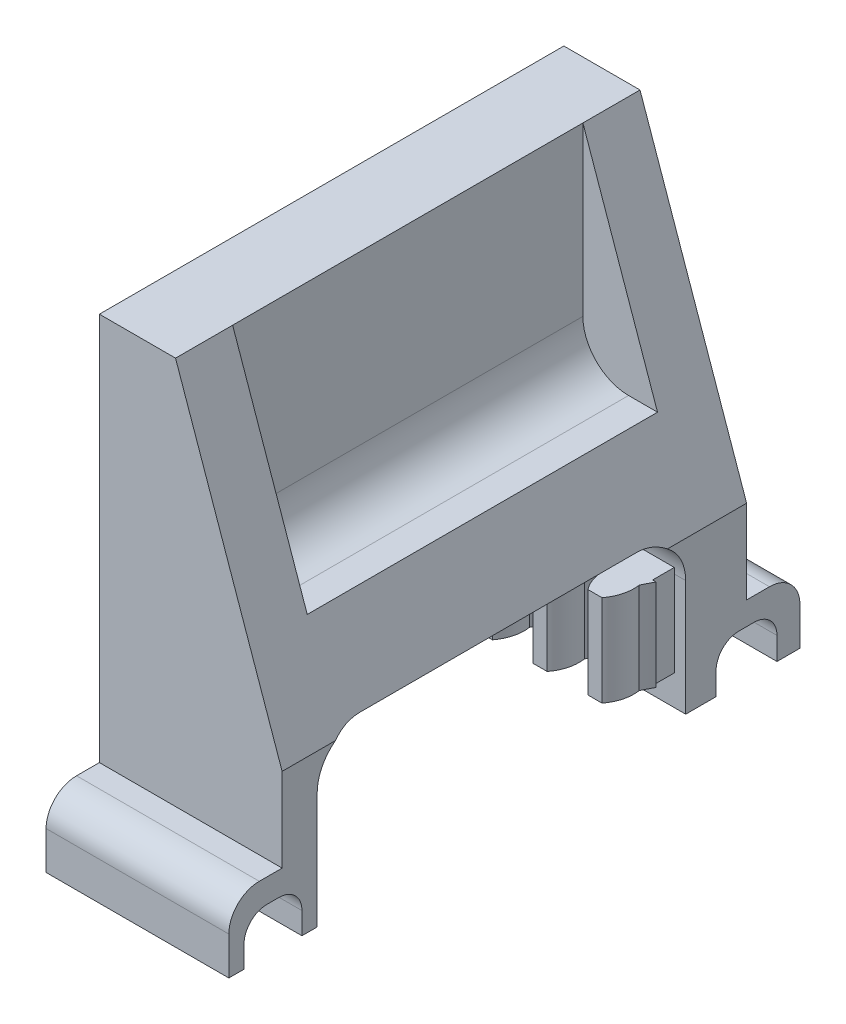
SolidWorks part; units mm, degrees
ref_plane "Front Plane" through (0, 0, 0) normal (0, 0, 1) x (1, 0, 0)
ref_plane "Top Plane" through (0, 0, 0) normal (0, 1, 0) x (1, 0, 0)
ref_plane "Right Plane" through (0, 0, 0) normal (1, 0, 0) x (0, 0, -1)
sketch "Sketch1" plane through (0, 0, 0) normal (0, 0, 1) x (1, 0, 0)
  line L0 (0, 0) -> (0, -30)
  line L1 (0, -30) -> (12, -30)
  line L2 (12, -30) -> (12, -20)
  line L3 (12, -20) -> (5, 0)
  line L4 (5, 0) -> (0, 0)
  dimension "D1" = 30
  dimension "D2" = 12
  dimension "D3" = 10
  dimension "D4" = 5
extrude "Boss-Extrude1" add sketch "Sketch1" against normal blind 30.5
sketch "Sketch4" plane through (0, 0, 0) normal (-1, 0, 0) x (0, 0, 1)
  line L0 (-30.5, 0) -> (-30.5, -30) construction
  line L1 (-26.5, -19.3999) -> (-2.3, -19.3999)
  line L2 (-26.5, -19.3999) -> (-26.5, -32.3999)
  line L3 (-26.5, -32.3999) -> (-2.3, -32.3999)
  line L4 (-2.3, -19.3999) -> (-2.3, -32.3999)
  point P4 (-26.5, -25.8999)
  dimension "D1" = 24.2
  dimension "D2" = 13
  dimension "D3" = 4
extrude "Cut-Extrude2" cut sketch "Sketch4" against normal blind 25 contours L2 L1 L4 L3
ref_plane "Plane1" through (0, 0, -15.25) normal (0, 0, 1) x (1, 0, 0)
sketch "Sketch6" plane through (0, 0, -15.25) normal (0, 0, 1) x (1, 0, 0)
  line L0 (5, 0) -> (5, -14)
  line L1 (5, -14) -> (9.9, -14)
  line L2 (12, -20) -> (5, 0) construction
  line L3 (9.9, -14) -> (5, 0)
  dimension "D1" = 14
extrude "Cut-Extrude4" cut sketch "Sketch6" against normal mid plane 23
ref_plane "Plane2" through (0, -26.4, 0) normal (0, 1, 0) x (1, 0, 0)
ref_plane "Plane3" through (0, -28, 0) normal (0, 1, 0) x (1, 0, 0)
sketch "Sketch7" plane through (0, -28, 0) normal (0, 1, 0) x (1, 0, 0)
  line L0 (11.2768, 26.75) -> (-19.7232, 26.75)
  line L62 (-6.6, 15.25) -> (6.6, 15.25) construction
  line L162 (11.2768, 26.75) -> (11.2768, 25.05)
  line L172 (-19.7232, 25.05) -> (-19.7232, 26.75)
  line L243 (11.2768, 25.05) -> (-19.7232, 25.05)
  dimension "D2" = 31
  dimension "D3" = 1.7
  dimension "D7" = 11.5
extrude "Boss-Extrude3" add sketch "Sketch7" along normal blind 6
sketch "Sketch10" plane through (0, -28, 0) normal (0, 1, 0) x (1, 0, 0)
  line L1 (10.1614, 22.3812) -> (10.1614, 23.4692) construction
  line L2 (10.6216, 22.3812) -> (9.7011, 22.3812)
  line L4 (-19.7232, 25.05) -> (11.2768, 25.05) construction
  line L5 (8.8114, 25.05) -> (11.5114, 25.05)
  arc A0 (10.6216, 22.3812) -> (11.1326, 24.3117) centre (8.6412, 23.9382) ccw
  arc A1 (11.1326, 24.3117) -> (11.5114, 25.05) centre (19.4957, 20.4874) cw
  arc A2 (9.1902, 24.3117) -> (8.8114, 25.05) centre (0.827, 20.4874) ccw
  arc A3 (9.7011, 22.3812) -> (9.1902, 24.3117) centre (11.6815, 23.9382) cw
  point P7 (9.3814, 24.3567)
  point P15 (9.6677, 22.4246)
  point P16 (9.1902, 24.3117)
  dimension "D1" = 2.7
extrude "Boss-Extrude4" add sketch "Sketch10" along normal blind 6
pattern_linear "LPattern1" count 8 spacing 3.6 along (-1, 0, 0) of "Boss-Extrude4"
sketch "Sketch11" plane through (0, 0, -30.5) normal (0, 0, -1) x (-1, 0, 0)
  line L0 (-12, -30) -> (-12, -20) construction
  line L1 (-12, -25.5) -> (0, -25.5)
  line L2 (-12, -25.5) -> (-12, -30)
  line L3 (-12, -30) -> (0, -30)
  line L4 (0, -25.5) -> (0, -30)
  dimension "D1" = 4.5
extrude "Boss-Extrude5" add sketch "Sketch11" along normal blind 3.5
fillet "Fillet1" radius 2 1 edges at (6, -25.5, -34)
mirror "Mirror1" about plane through (0, 0, -15.25) normal (0, 0, 1) of "Boss-Extrude5"
fillet "Fillet2" radius 2 1 edges at (6, -25.5, 3.5)
fillet "Fillet5" radius 3 3 edges at (5, -14, -15.25) (5.895, -19.3999, -2.3) (5.895, -19.3999, -26.5)
sketch "Sketch12" plane through (0, 0, 0) normal (-1, 0, 0) x (0, 0, 1)
  line L0 (-15.25, -20.6354) -> (-15.25, -36.9741) construction
  line L1 (-32.4946, -27.0184) -> (-28.4946, -27.0184)
  line L2 (-32.4946, -27.0184) -> (-32.4946, -30.5184)
  line L3 (-32.4946, -30.5184) -> (-28.4946, -30.5184)
  line L4 (-28.4946, -27.0184) -> (-28.4946, -30.5184)
  line L5 (-2.3, -30) -> (-2.3, -22.3999) construction
  line L11 (-15.25, -16.5) -> (-15.25, 16.5) construction
  line L12 (2.5, -30.5644) -> (-1.3, -30.5644)
  line L13 (-1.3, -27.0644) -> (-1.3, -30.5644)
  line L14 (2.5, -27.0644) -> (-1.3, -27.0644)
  line L15 (2.5, -27.0644) -> (2.5, -30.5644)
  dimension "D1" = 4
  dimension "D2" = 3.5
  dimension "D3" = 1
extrude "Cut-Extrude5" cut sketch "Sketch12" against normal up to surface (12 mm away) up to face at (12, -25.043, -29.9997)
fillet "Fillet6" radius 1.5 4 edges at (6, -27.0184, -32.4946) (6, -27.0184, -28.4946) (6, -27.0644, 2.5) (6, -27.0644, -1.3)
